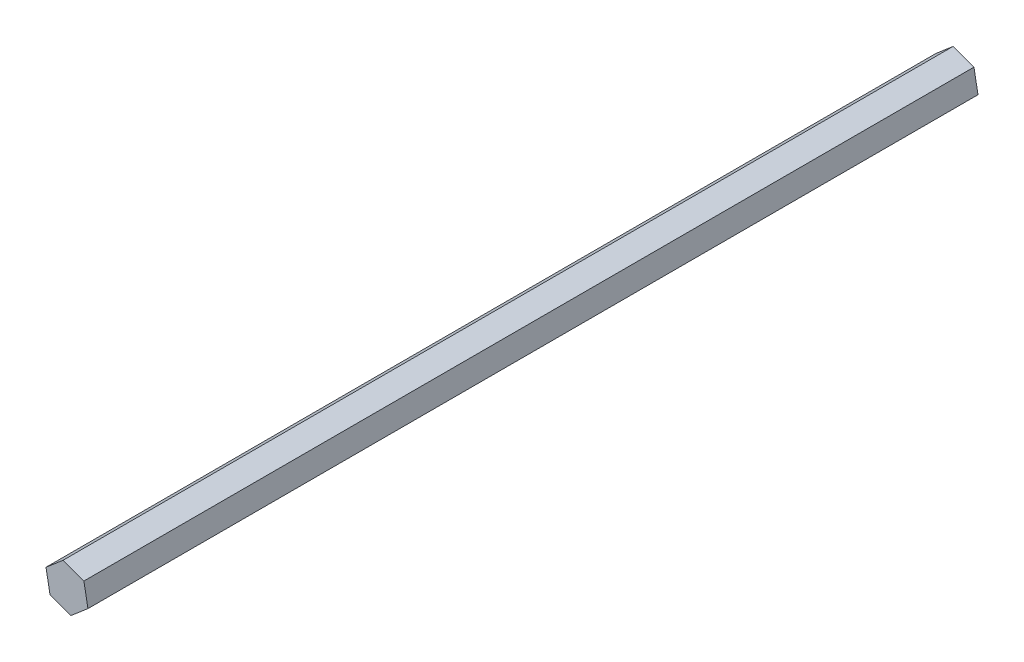
SolidWorks part; units mm, degrees
ref_plane "Front Plane" through (0, 0, 0) normal (0, 0, 1) x (1, 0, 0)
ref_plane "Top Plane" through (0, 0, 0) normal (0, 1, 0) x (1, 0, 0)
ref_plane "Right Plane" through (0, 0, 0) normal (1, 0, 0) x (0, 0, -1)
sketch "Sketch1" plane through (0, 0, 0) normal (0, 0, 1) x (1, 0, 0)
  line L1 (3.7707, -1.3349) -> (3.0414, 2.5981)
  line L2 (3.0414, 2.5981) -> (-0.7293, 3.933)
  line L3 (-0.7293, 3.933) -> (-3.7707, 1.3349)
  line L4 (-3.7707, 1.3349) -> (-3.0414, -2.5981)
  line L5 (-3.0414, -2.5981) -> (0.7293, -3.933)
  line L6 (0.7293, -3.933) -> (3.7707, -1.3349)
  circle A0 centre (0, 0) radius 4 construction
  circle A1 centre (0, 0) radius 3.4641 construction
  dimension "D1" = 8
  dimension "D2" = 2.5981
  dimension "D3" = 4
extrude "Boss-Extrude1" add sketch "Sketch1" along normal blind 160
